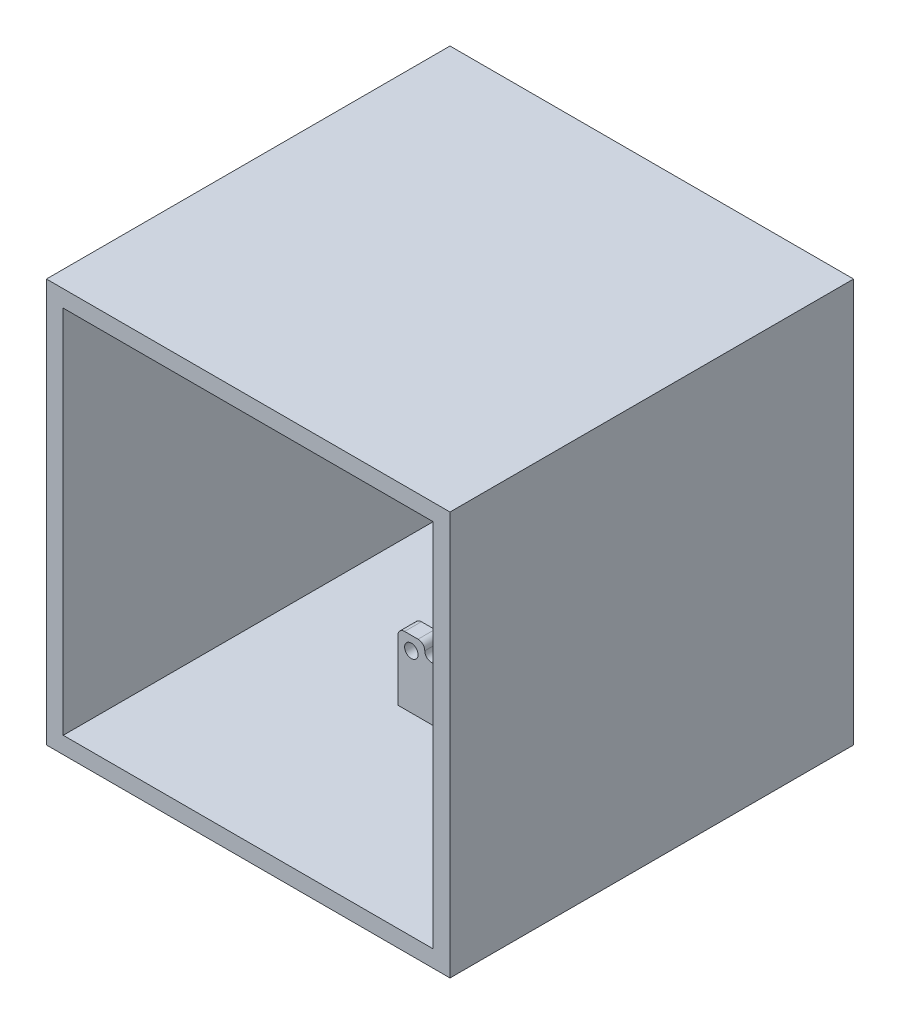
SolidWorks part; units mm, degrees
ref_plane "Front Plane" through (0, 0, 0) normal (0, 0, 1) x (1, 0, 0)
ref_plane "Top Plane" through (0, 0, 0) normal (0, 1, 0) x (1, 0, 0)
ref_plane "Right Plane" through (0, 0, 0) normal (1, 0, 0) x (0, 0, -1)
sketch "Sketch1" plane through (0, 0, 0) normal (0, 0, 1) x (1, 0, 0)
  line L1 (-38.1, 38.1) -> (38.1, 38.1)
  line L2 (-38.1, 38.1) -> (-38.1, -38.1)
  line L3 (-38.1, -38.1) -> (38.1, -38.1)
  line L4 (38.1, 38.1) -> (38.1, -38.1)
  line L5 (-38.1, 38.1) -> (38.1, -38.1) construction
  line L6 (-38.1, -38.1) -> (38.1, 38.1) construction
  point P0 (0, 0)
  dimension "D1" = 76.2
  dimension "D2" = 76.2
extrude "Boss-Extrude1" add sketch "Sketch1" along normal blind 38.1 and the other way blind 38.1
shell "Shell1" thickness 3.175 removed face at (0, 0, 38.1)
sketch "Sketch2" plane through (0, 34.925, 0) normal (0, -1, 0) x (1, 0, 0)
  line L0 (-38.1, 1.5875) -> (38.1, 1.5875) construction
  line L3 (-38.1, -38.1) -> (-38.1, 38.1) construction
  line L4 (38.1, -38.1) -> (38.1, 38.1) construction
  line L13 (-38.1, -1.5875) -> (38.1, -1.5875) construction
  line L14 (0, -1.5875) -> (0, 1.5875) construction
  line L16 (-8.255, 1.5875) -> (8.255, 1.5875)
  line L17 (-8.255, 1.5875) -> (-8.255, -1.5875)
  line L18 (-8.255, -1.5875) -> (8.255, -1.5875)
  line L19 (8.255, 1.5875) -> (8.255, -1.5875)
  point P15 (0, 1.5875)
  point P16 (0, 0)
  dimension "D1" = 3.175
  dimension "D2" = 16.51
extrude "Boss-Extrude2" add sketch "Sketch2" along normal blind 12.7
sketch "Sketch3" plane through (0, 0, 1.5875) normal (0, 0, 1) x (1, 0, 0)
  line L0 (8.255, 34.925) -> (-8.255, 34.925) construction
  line L1 (-5.715, 24.765) -> (5.715, 24.765) construction
  line L2 (8.255, 22.225) -> (-8.255, 22.225) construction
  line L3 (0, 22.225) -> (0, 24.765) construction
  line L5 (-3.175, 22.225) -> (3.175, 22.225)
  line L6 (-3.175, 22.225) -> (-3.175, 24.765)
  line L7 (-3.175, 24.765) -> (3.175, 24.765)
  line L8 (3.175, 22.225) -> (3.175, 24.765)
  circle A0 centre (-5.715, 24.765) radius 1.27
  circle A1 centre (5.715, 24.765) radius 1.27
  point P14 (0, 24.765)
  dimension "D1" = 2.54
  dimension "D3" = 11.43
  dimension "D2" = 10.16
  dimension "D4" = 2.54
extrude "Cut-Extrude1" cut sketch "Sketch3" against normal blind 12.7 and the other way blind 12.7
ref_plane "Plane1" through (0, 0, 0) normal (0, 1, 0) x (1, 0, 0)
fillet "Fillet1" radius 1.27 6 edges at (-3.175, 24.765, 0) (8.255, 22.225, 0) (3.175, 22.225, 0) (-3.175, 22.225, 0) (-8.255, 22.225, 0) (3.175, 24.765, 0)
mirror "Mirror2" about plane through (0, 0, 0) normal (0, 1, 0) of "Fillet1", "Boss-Extrude2", "Cut-Extrude1"
chamfer "Chamfer1" distance 7.62 angle 45 2 edges at (0, 34.925, -1.5875) (0, -34.925, -1.5875)
